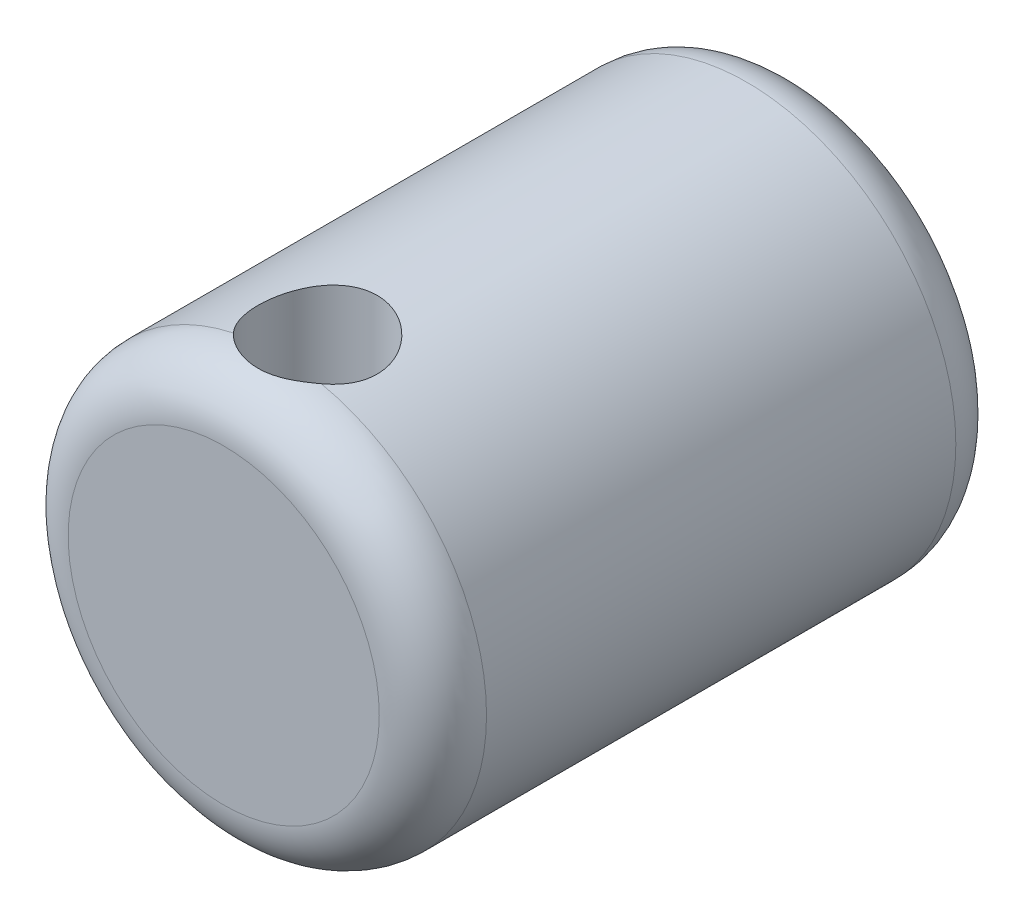
SolidWorks part; units mm, degrees
note: The reader was unsure of these and kept them because the rebuilt part matched: shared geometry of "Sketch2<2>".
ref_plane "Front Plane" through (0, 0, 0) normal (0, 0, 1) x (1, 0, 0)
ref_plane "Top Plane" through (0, 0, 0) normal (0, 1, 0) x (1, 0, 0)
ref_plane "Right Plane" through (0, 0, 0) normal (1, 0, 0) x (0, 0, -1)
sketch "Sketch2" plane through (0, 0, 0) normal (0, 0, 1) x (1, 0, 0)
  circle A1 centre (0, 0) radius 2.413
  circle A3 centre (0, 0) radius 4.953
  circle A4 centre (0, 0) radius 1.9939
  circle A5 centre (0, 0) radius 1.9939 construction
  circle M3 centre (0, 0) radius 1.9939
  dimension "D3" = 4.826
  dimension "D4" = 2.54
  dimension "D2" = 0
extrude "Boss-Extrude1" add sketch "Sketch2" against normal blind 8.89
extrude "Boss-Extrude2" add sketch "Sketch2<2>" along normal blind 4.7625 contours M3 | A3 A1 | A1 M3
sketch "Sketch2<2>" plane through (0, 0, 0) normal (0, 0, 1) x (1, 0, 0) same geometry as "Sketch2"
fillet "Fillet1" [suppressed] radius 2.54
ref_plane "Plane1" through (0, 4.953, 0) normal (0, 1, 0) x (1, 0, 0)
hole_wizard "#46 (0.081) Diameter Hole2" [suppressed] positions "Sketch7" profile "Sketch6" hole size "#46" standard "ANSI Inch"
sketch "Sketch7" plane through (0, 4.5339, 0) normal (0, 1, 0) x (1, 0, 0)
  point P0 (0, -1.27)
  dimension "D1" = 1.27
sketch "Sketch6" plane through (0, 4.5339, 1.27) normal (1, 0, 0) x (0, 0, 1)
  line L0 (0, 0) -> (0, 9.0678)
  line L1 (0, 9.0678) -> (1.0287, 9.0678)
  line L2 (1.0287, 9.0678) -> (1.0287, 0)
  line L5 (1.0287, 0) -> (0, 0)
  line L11 (0, -6.35) -> (0, 107.95) construction
  dimension "Thru Hole Dia." = 2.0574
  dimension "Thru Hole Depth" = 9.0678
sketch "Sketch8" plane through (0, 0, 0) normal (0, 1, 0) x (1, 0, 0)
  circle A0 centre (0, -2.54) radius 1.4111
  dimension "D1" = 2.8222
extrude "Cut-Extrude1" cut sketch "Sketch8" against normal up to next and the other way up to next
fillet "Fillet2" radius 1.27 2 edges at (4.953, 0, -8.89) (4.953, 0, 4.7625)
